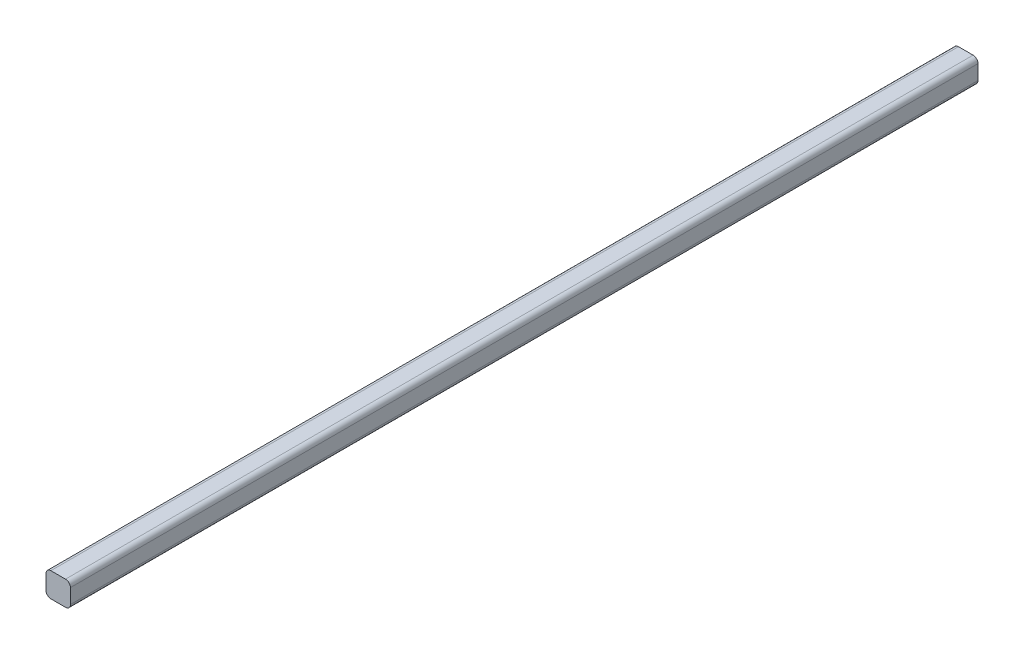
SolidWorks part; units mm, degrees
ref_plane "Plan de face" through (0, 0, 0) normal (0, 0, 1) x (1, 0, 0)
ref_plane "Plan de dessus" through (0, 0, 0) normal (0, 1, 0) x (1, 0, 0)
ref_plane "Plan de droite" through (0, 0, 0) normal (1, 0, 0) x (0, 0, -1)
sketch "Esquisse1" plane through (0, 0, 0) normal (0, 0, 1) x (1, 0, 0)
  line L1 (0, 0) -> (50, 0)
  line L2 (0, 0) -> (0, 50)
  line L3 (0, 50) -> (50, 50)
  line L4 (50, 0) -> (50, 50)
  dimension "D1" = 50
  dimension "D2" = 50
extrude "Boss.-Extru.1" add sketch "Esquisse1" along normal blind 1860
fillet "Congé1" radius 10 4 edges at (0, 0, 930) (50, 0, 930) (0, 50, 930) (50, 50, 930)
